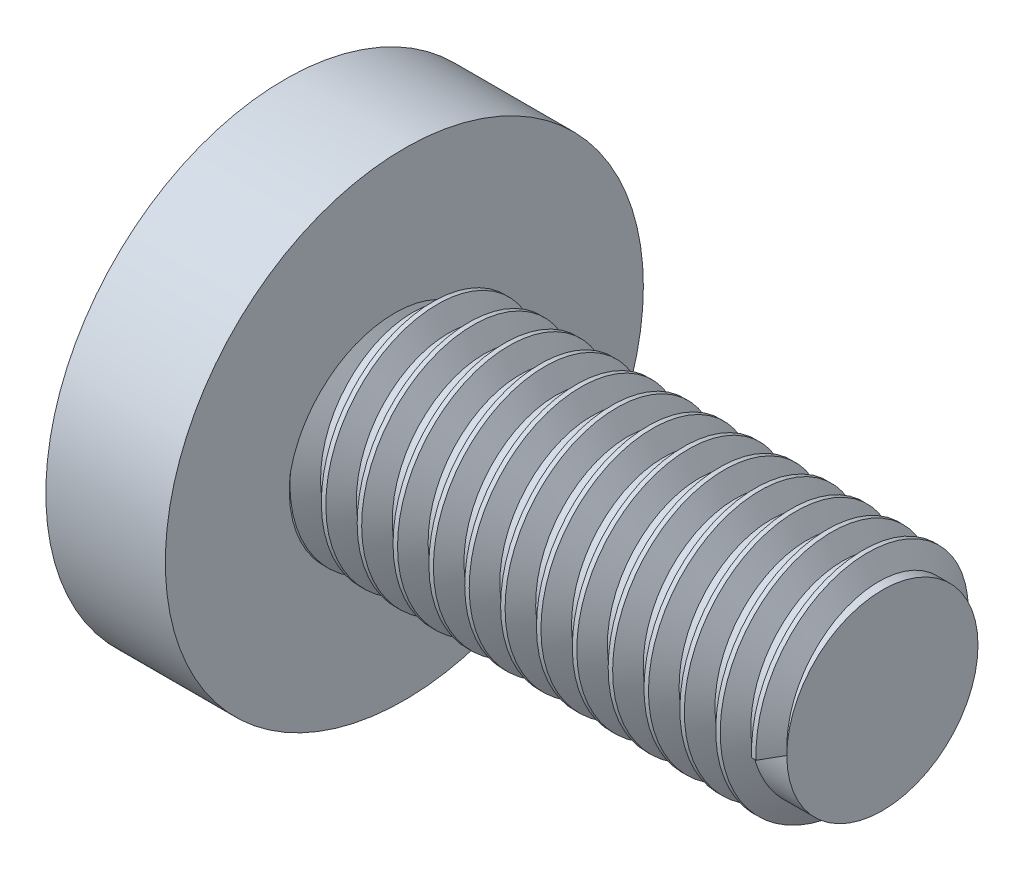
SolidWorks part; units mm, degrees
ref_plane "Front Plane" through (0, 0, 0) normal (0, 0, 1) x (1, 0, 0)
ref_plane "Top Plane" through (0, 0, 0) normal (0, 1, 0) x (1, 0, 0)
ref_plane "Right Plane" through (0, 0, 0) normal (1, 0, 0) x (0, 0, -1)
sketch "Sketch4" plane through (0, 0, 0) normal (0, 0, 1) x (1, 0, 0)
  line L0 (0, 0) -> (0, 10)
  line L1 (0, 10) -> (5, 10)
  line L2 (5, 10) -> (5, 4)
  line L3 (5, 4) -> (25, 4)
  line L4 (25, 4) -> (25, 0)
  line L5 (25, 0) -> (0, 0)
  point P3 (5, 7)
  dimension "D1" = 25
  dimension "D2" = 4
  dimension "D4" = 5
  dimension "D6" = 6
revolve "Revolve1" add sketch "Sketch4" angle 360 about L5
thread "Diş1" pitch 1.5 method extrude profile "Diş Profili2" start angle 0, offset 0, length 20, pitch 1.5, diameter 8
ref_plane "Düzlem2" through (25, 0, 4) normal (0, -1, 0) x (0, 0, 1)
sketch "Diş Profili2" plane through (25, 0, 4) normal (0, -1, 0) x (0, 0, 1)
  line L0 (0, 0) -> (0, 1.5) construction
  line L1 (0, 0) -> (0.8119, 0.4687)
  line L2 (0.8119, 0.4687) -> (0.8119, 0.6562)
  line L3 (0.8119, 0.6562) -> (0, 1.125)
  line L4 (0.8119, 0.5625) -> (0, 0.5625) construction
  line L11 (0, 0) -> (0, 1.125)
  point P2 (0, 0)
  dimension "Pitch" = 1.5
  dimension "Profile_Angle" = 60
  dimension "Profile_Land" = 0.1875
  dimension "Profile_Height" = 0.8119
